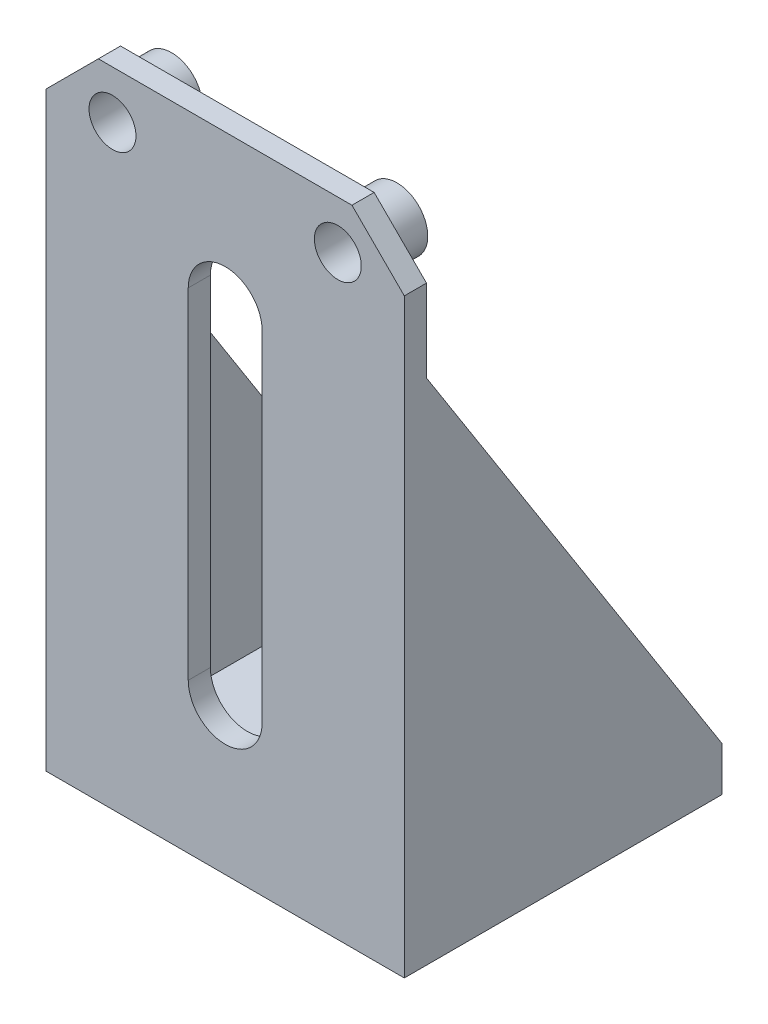
SolidWorks part; units mm, degrees
ref_plane "Front Plane" through (0, 0, 0) normal (0, 0, 1) x (1, 0, 0)
ref_plane "Top Plane" through (0, 0, 0) normal (0, 1, 0) x (1, 0, 0)
ref_plane "Right Plane" through (0, 0, 0) normal (1, 0, 0) x (0, 0, -1)
sketch "Sketch1" plane through (0, 0, 0) normal (0, 0, 1) x (1, 0, 0)
  line L0 (-33.4213, -6) -> (-33.4213, 36.5)
  line L2 (9.0787, 36.5) -> (9.0787, -6)
  line L3 (9.0787, -6) -> (-33.4213, -6)
  line L5 (-33.4213, 36.5) -> (9.0787, 36.5) construction
  line L7 (-28.4213, 77.55) -> (4.0787, 77.55)
  line L10 (-33.4213, 36.5) -> (-33.4213, 72.55)
  line L11 (-33.4213, 72.55) -> (-28.4213, 77.55)
  line L12 (-12.1713, 36.5) -> (-12.1713, 77.55) construction
  line L13 (9.0787, 36.5) -> (9.0787, 72.55)
  line L14 (9.0787, 72.55) -> (4.0787, 77.55)
  circle A0 centre (2.9277, 30.5) radius 1.55
  circle A1 centre (2.9277, -0.5) radius 1.5
  circle A2 centre (-27.6713, -0.5) radius 1.5
  circle A3 centre (-28.0723, 30.5) radius 1.5
  circle A4 centre (-12.1713, 15.25) radius 11
  circle A5 centre (-27.4213, 71.55) radius 3.175
  circle A6 centre (3.0787, 71.55) radius 3.175
  dimension "D5" = 22
  dimension "D10" = 3.1
  dimension "D13" = 6
  dimension "D16" = 6.35
  dimension "D1" = 42.5
  dimension "D2" = 42.5
  dimension "D3" = 31
  dimension "D4" = 31
  dimension "D6" = 62.3
  dimension "D7" = 21.25
  dimension "D8" = 21.25
  dimension "D9" = 5
  dimension "D11" = 5.5
  dimension "D12" = 5.5
  dimension "D14" = 6
  dimension "D15" = 6
extrude "Boss-Extrude1" add sketch "Sketch1" along normal blind 3
sketch "Sketch2" plane through (0, 0, 0) normal (0, 0, -1) x (-1, 0, 0)
  circle A0 centre (-3.0787, 71.55) radius 3.175
  circle A1 centre (27.4213, 71.55) radius 3.175
  circle A2 centre (-3.0787, 71.55) radius 4.175
  circle A3 centre (27.4213, 71.55) radius 4.175
  dimension "D1" = 6.35
  dimension "D2" = 6.35
  dimension "D3" = 1
  dimension "D4" = 1
extrude "Boss-Extrude2" add sketch "Sketch2" along normal blind 3
sketch "Sketch3" plane through (0, 0, -3) normal (0, 0, -1) x (-1, 0, 0)
  circle A0 centre (-3.0787, 71.55) radius 4.175
  circle A1 centre (27.4213, 71.55) radius 4.175
  dimension "D1" = 8.35
  dimension "D2" = 8.35
extrude "Boss-Extrude3" add sketch "Sketch3" along normal blind 2
sketch "Sketch4" plane through (0, 0, 0) normal (0, 0, -1) x (-1, 0, 0)
  line L0 (33.4213, -6) -> (-9.0787, -6)
  line L2 (-9.0787, -9) -> (34.4213, -9)
  line L4 (-9.0787, -3) -> (-12.0787, -3)
  line L5 (-9.0787, -6) -> (-9.0787, 72.55) construction
  line L6 (-12.0787, -3) -> (-12.0787, -9)
  line L7 (-12.0787, -9) -> (-9.0787, -9)
  line L8 (-9.0787, -6) -> (-9.0787, -3)
  line L10 (36.4213, -9) -> (34.4213, -9)
  line L11 (36.4213, -3) -> (36.4213, -9)
  line L12 (33.4213, -3) -> (36.4213, -3)
  line L13 (33.4213, -6) -> (33.4213, -3)
  dimension "D1" = 3
  dimension "D2" = 3
  dimension "D4" = 3
extrude "Boss-Extrude4" add sketch "Sketch4" along normal blind 40 and the other way blind 3 separate body
sketch "Sketch5" plane through (0, 0, 3) normal (0, 0, 1) x (1, 0, 0)
  line L1 (9.0787, 48.0314) -> (9.0787, 43.0314)
  line L2 (9.0787, -6) -> (9.0787, 72.55) construction
  line L3 (9.0787, 48.0314) -> (12.0787, 48.0314)
  line L4 (12.0787, 48.0314) -> (12.0787, 43.0314)
  line L5 (12.0787, 43.0314) -> (9.0787, 43.0314)
  line L6 (-33.4213, 45.5314) -> (9.0787, 45.5314) construction
  line L11 (-12.1713, 45.5314) -> (-12.1713, 51.3356) construction
  line L12 (-36.4213, 48.0314) -> (-36.4213, 43.0314)
  line L16 (-33.4213, 48.0314) -> (-36.4213, 48.0314)
  line L17 (-33.4213, 48.0314) -> (-33.4213, 43.0314)
  line L18 (-36.4213, 43.0314) -> (-33.4213, 43.0314)
  circle A0 centre (2.9277, 30.5) radius 1.55 construction
  dimension "D2" = 12.5314
  dimension "D1" = 3
  dimension "D3" = 42.5
  dimension "D4" = 5
  dimension "3" = 3
  dimension "D5" = 3
extrude "Boss-Extrude5" add sketch "Sketch5" against normal blind 3
sketch "Sketch6" plane through (9.0787, 0, 0) normal (1, 0, 0) x (0, 0, -1)
  line L0 (0, 48.0314) -> (40, -3)
  line L1 (0, 43.0314) -> (36.0808, -3)
  line L2 (0, 48.0314) -> (0, 43.0314)
  line L3 (36.0808, -3) -> (40, -3)
  line L4 (-3, -3) -> (40, -3) construction
extrude "Boss-Extrude7" add sketch "Sketch6" along normal blind 3
sketch "Sketch8" plane through (-36.4213, 0, 0) normal (-1, 0, 0) x (0, 0, 1)
  line L0 (0, 48.0314) -> (0, 43.0314)
  line L1 (0, 43.0314) -> (-36.0808, -3)
  line L2 (-36.0808, -3) -> (-40, -3)
  line L3 (-40, -3) -> (0, 48.0314)
extrude "Boss-Extrude9" add sketch "Sketch8" against normal blind 3
sketch "Sketch9" plane through (0, 0, 3) normal (0, 0, 1) x (1, 0, 0)
  circle A0 centre (2.9277, 30.5) radius 1.55
  circle A1 centre (-28.0723, 30.5) radius 1.5
  circle A2 centre (-27.6713, -0.5) radius 1.5
  circle A3 centre (2.9277, -0.5) radius 1.5
  circle A4 centre (-12.1713, 15.25) radius 11
extrude "Boss-Extrude10" add sketch "Sketch9" against normal blind 3
sketch "Sketch10" plane through (0, 0, 3) normal (0, 0, 1) x (1, 0, 0)
  line L0 (-12.1713, 77.55) -> (-12.1713, -9) construction
  line L1 (4.0787, 77.55) -> (-28.4213, 77.55) construction
  line L2 (12.0787, -9) -> (-36.4213, -9) construction
  line L3 (-12.1713, 57.275) -> (-12.1713, 11.275) construction
  line L4 (-7.1713, 57.275) -> (-7.1713, 11.275)
  line L5 (-17.1713, 57.275) -> (-17.1713, 11.275)
  line L6 (-33.4213, 34.275) -> (9.0787, 34.275) construction
  line L7 (-33.4213, -3) -> (-33.4213, 43.0314) construction
  line L8 (9.0787, -3) -> (9.0787, 43.0314) construction
  arc A0 (-7.1713, 57.275) -> (-17.1713, 57.275) centre (-12.1713, 57.275) ccw
  arc A1 (-17.1713, 11.275) -> (-7.1713, 11.275) centre (-12.1713, 11.275) ccw
  point P8 (-12.1713, 34.275)
  dimension "D1" = 23
  dimension "D2" = 5
extrude "Cut-Extrude1" cut sketch "Sketch10" against normal blind 3
sketch "Sketch11" plane through (0, 0, 3) normal (0, 0, 1) x (1, 0, 0)
  line L0 (-12.1713, 77.55) -> (-12.1713, -9) construction
  line L1 (4.0787, 77.55) -> (-28.4213, 77.55) construction
  line L2 (12.0787, -9) -> (-36.4213, -9) construction
  line L3 (-33.4213, 72.55) -> (-36.4213, 72.55)
  line L9 (-33.4213, -3) -> (-36.4213, -3)
  line L11 (-36.4213, -3) -> (-36.4213, 72.55)
  line L12 (-33.4213, -3) -> (-33.4213, 72.55)
  line L13 (9.0787, -3) -> (12.0787, -3)
  line L14 (12.0787, -3) -> (12.0787, 72.55)
  line L15 (9.0787, 72.55) -> (12.0787, 72.55)
  line L16 (9.0787, -3) -> (9.0787, 72.55)
extrude "Boss-Extrude11" add sketch "Sketch11" against normal blind 3
chamfer "Chamfer1" distance 3 angle 45 2 edges at (-36.4213, 72.55, 1.5) (12.0787, 72.55, 1.5)
sketch "Sketch12" plane through (12.0787, 0, 0) normal (1, 0, 0) x (0, 0, -1)
  line L0 (-3, 64.55) -> (-3, -9)
  line L1 (-3, 69.55) -> (-3, -9) construction
  line L2 (-3, -9) -> (40, -9)
  line L3 (40, -9) -> (40, -3)
  line L4 (40, -3) -> (-3, 64.55)
extrude "Boss-Extrude12" add sketch "Sketch12" against normal blind 3
sketch "Sketch13" plane through (-36.4213, 0, 0) normal (-1, 0, 0) x (0, 0, 1)
  line L0 (3, -9) -> (3, 64.55)
  line L1 (3, -9) -> (3, 69.55) construction
  line L2 (3, 64.55) -> (-40, -3)
  line L3 (-40, -3) -> (-40, -9)
  line L4 (-40, -9) -> (3, -9)
extrude "Boss-Extrude13" add sketch "Sketch13" against normal blind 3
sketch "Sketch14" plane through (0, 0, 3) normal (0, 0, 1) x (1, 0, 0)
  line L0 (-36.4213, 69.55) -> (-36.4213, 70.9642)
  line L1 (-36.4213, 70.9642) -> (-29.3355, 78.05)
  line L2 (-29.3355, 78.05) -> (4.9929, 78.05)
  line L3 (-12.1713, 78.05) -> (-12.1713, 77.55)
  line L4 (4.0787, 77.55) -> (-28.4213, 77.55) construction
  line L5 (4.0787, 77.55) -> (-28.4213, 77.55)
  line L6 (-28.4213, 77.55) -> (-36.4213, 69.55)
  line L7 (-12.1713, 77.55) -> (-12.1713, 88.8912) construction
  line L8 (12.0787, 70.9642) -> (4.9929, 78.05)
  line L9 (12.0787, 69.55) -> (12.0787, 70.9642)
  line L10 (4.0787, 77.55) -> (12.0787, 69.55)
  line M12 (12.0787, 69.55) -> (9.0787, 72.55)
  line M13 (9.0787, 72.55) -> (4.0787, 77.55)
  line M14 (4.0787, 77.55) -> (-28.4213, 77.55)
  dimension "D1" = 1
  dimension "D2" = 0.5
extrude "Boss-Extrude14" add sketch "Sketch14" against normal blind 3 contours L9 L8 L2 L3 M12 M14 M13 | L5 L6 L0 L1 L2 L8 L9 L10 region at (-11.9143, 77.8, 3)
